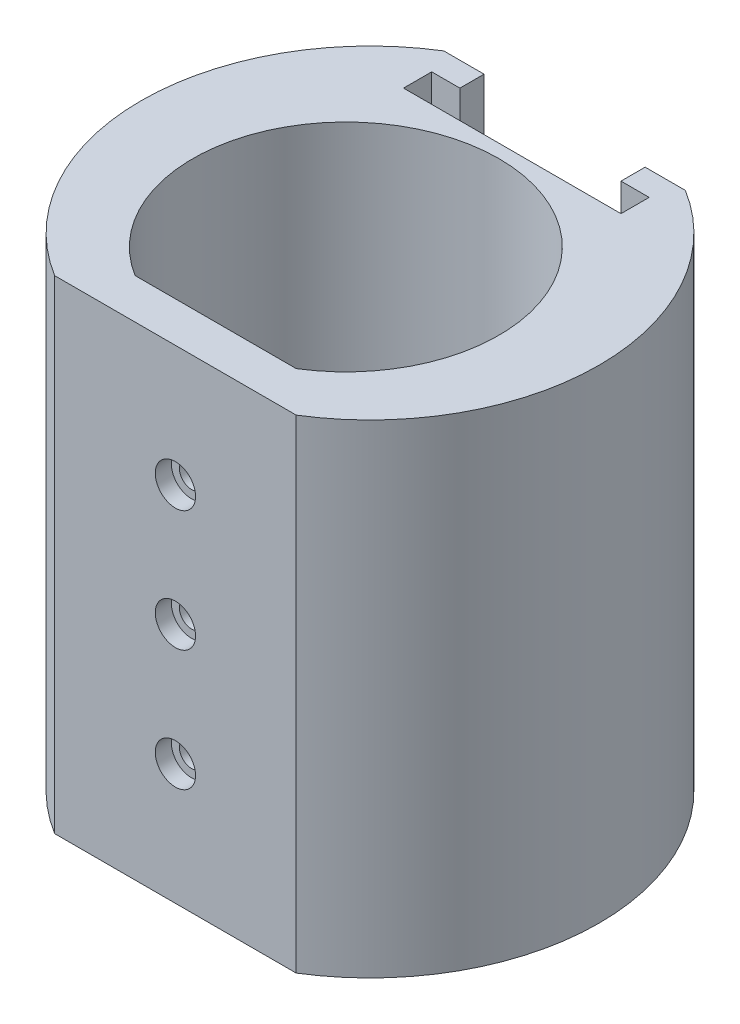
SolidWorks part; units mm, degrees
ref_plane "Front Plane" through (0, 0, 0) normal (0, 0, 1) x (1, 0, 0)
ref_plane "Top Plane" through (0, 0, 0) normal (0, 1, 0) x (1, 0, 0)
ref_plane "Right Plane" through (0, 0, 0) normal (1, 0, 0) x (0, 0, -1)
sketch "Sketch1" plane through (0, 0, 0) normal (0, 1, 0) x (1, 0, 0)
  line L0 (-10, -16.1614) -> (10, -16.1614)
  line L1 (-15, -21.1614) -> (15, -21.1614)
  line L2 (-15, 27.1614) -> (15, 27.1614)
  arc A0 (10, -16.1614) -> (-10, -16.1614) centre (0, 0) ccw
  arc A1 (15, -21.1614) -> (15, 27.1614) centre (0, 3) ccw
  arc A2 (-15, 27.1614) -> (-15, -21.1614) centre (0, 3) ccw
  point P5 (0, -21.1614)
  dimension "D1" = 38.01
  dimension "D4" = 3
  dimension "D2" = 20
  dimension "D3" = 5
  dimension "D5" = 30
  dimension "D6" = 30
extrude "Boss-Extrude1" add sketch "Sketch1" along normal mid plane 60
sketch "Sketch4" plane through (0, 30, 0) normal (0, 1, 0) x (1, 0, 0)
  line L0 (-10, 27.1614) -> (-10, 24.1614)
  line L2 (10, 24.1614) -> (10, 27.1614)
  line L3 (10, 27.1614) -> (-10, 27.1614)
  line L4 (-10, 24.1614) -> (-13.5, 24.1614)
  line L5 (-13.5, 24.1614) -> (-13.5, 20.6614)
  line L6 (-13.5, 20.6614) -> (13.5, 20.6614)
  line L7 (13.5, 20.6614) -> (13.5, 24.1614)
  line L8 (13.5, 24.1614) -> (10, 24.1614)
  line L9 (15, 27.1614) -> (-15, 27.1614) construction
  point P11 (0, 20.6614)
  point P12 (0, 27.1614)
  dimension "D1" = 3
  dimension "D2" = 27
  dimension "D3" = 3.5
  dimension "D4" = 20
extrude "Cut-Extrude1" cut sketch "Sketch4" against normal offset from surface (50 mm away) 10 up to face at (0, -30, -3)
sketch "Sketch5" plane through (0, 0, 21.1614) normal (0, 0, 1) x (1, 0, 0)
  circle A0 centre (0, 0) radius 1.5
  circle A1 centre (0, 0) radius 2.5
  dimension "D2" = 3
  dimension "D1" = 1
extrude "Cut-Extrude2" cut sketch "Sketch5" against normal up to surface (5 mm away) contours A0 region at (0, 0, 21.1614) up to face at (0, 0, 16.1614)
extrude "Cut-Extrude3" cut sketch "Sketch5<3>" against normal blind 2 contours A1 A0 region at (-2.4293, 0, 21.1614)
sketch "Sketch5<3>" plane through (0, 0, 21.1614) normal (0, 0, 1) x (1, 0, 0) same geometry as "Sketch5"
pattern_linear "LPattern1" count 2 spacing 15 along (0, -1, 0) count 2 spacing 15 along (0, 1, 0) of "Cut-Extrude3", "Cut-Extrude2" pattern seed only yes
